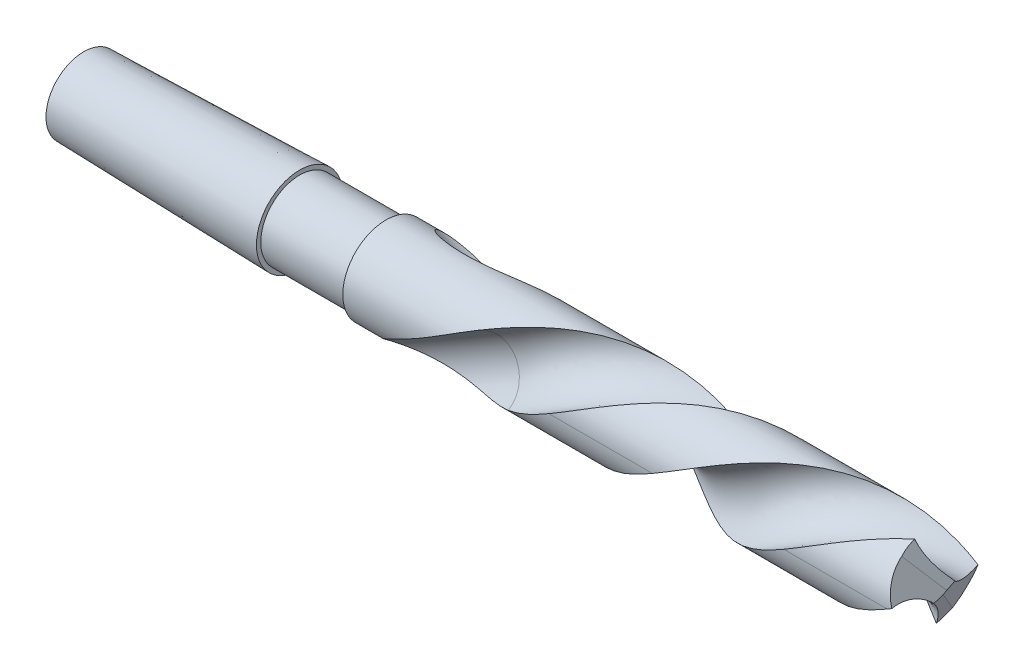
SolidWorks part; units mm, degrees
ref_plane "Ön Düzlem" through (0, 0, 0) normal (0, 0, 1) x (1, 0, 0)
ref_plane "Üst Düzlem" through (0, 0, 0) normal (0, 1, 0) x (1, 0, 0)
ref_plane "Sağ Düzlem" through (0, 0, 0) normal (1, 0, 0) x (0, 0, -1)
sketch "Çizim1" plane through (0, 0, 0) normal (0, 0, 1) x (1, 0, 0)
  line L9 (0, 0) -> (100, 0)
  line L10 (100, 0) -> (100, 5)
  line L11 (100, 5) -> (35, 5)
  line L12 (35, 5) -> (35, 4.5)
  line L13 (35, 4.5) -> (25, 4.5)
  line L14 (25, 4.5) -> (25, 5)
  line L15 (25, 5) -> (0, 4.37)
  line L16 (0, 4.37) -> (0, 0)
  point P2 (0, 0)
  dimension "D1" = 100
  dimension "D2" = 4.5
  dimension "D3" = 5
  dimension "D4" = 5
  dimension "D5" = 4.37
  dimension "D6" = 65
  dimension "D7" = 10
revolve "Döndür2" add sketch "Çizim1" angle 360 about L9
ref_plane "Düzlem2" through (51.25, 0, 0) normal (1, 0, 0) x (0, 0, -1)
ref_axis "Eksen3" through (100, 0, 0) along (-1, 0, 0)
ref_axis "Eksen4" through (51.25, 0, -5.5) along (0, 0, 1)
ref_plane "Düzlem3" through (38.4375, 22.1919, 0) normal (-0.866, -0.5, 0) x (0, 0, 1)
sketch "Çizim2" plane through (51.25, 0, 0) normal (1, 0, 0) x (0, 0, -1)
  circle A0 centre (0, 0) radius 5
  dimension "D1" = 10
curve "Helis/Spiral1" pitch 54.414 height 60 turns 1.1027
sketch "Çizim4" plane through (51.25, 0, 0) normal (1, 0, 0) x (0, 0, -1)
  circle A0 centre (0, 0) radius 5
  dimension "D1" = 10
curve "Helis/Spiral2" pitch 54.414 height 60 radius 5 left hand yes centre (51.25, 0, 0) axis (1, 0, 0) start towards (0, 0, 1)
sketch "Çizim5" plane through (38.4375, 22.1919, 0) normal (-0.866, -0.5, 0) x (0, 0, 1)
  line L0 (-5.5, -25.625) -> (5.5, -25.625) construction
  line L1 (0, -50) -> (0, -17.5) construction
  circle A0 centre (5, -25.625) radius 3.75
  dimension "D1" = 7.5
  dimension "D2" = 5
sweep "Kes-Süpür2" cut profiles "Çizim5" path "Helis/Spiral2" align with end faces yes
extrude "Kes-Ekstrüzyon3" cut sketch "Çizim5<2>" along normal through all
sketch "Çizim5<2>" plane through (38.4375, 22.1919, 0) normal (-0.866, -0.5, 0) x (0, 0, 1) same geometry as "Çizim5"
pattern_circular "Dairesel Kaplama2" count 2 over 360 about axis through (0, 0, 0) along (-1, 0, 0) of "Kes-Ekstrüzyon3", "Kes-Süpür2"
sketch "Çizim6" plane through (100, 0, 0) normal (1, 0, 0) x (0, 0, -1)
  line L0 (3.9159, 3.1089) -> (-3.9159, -3.1089)
  circle A0 centre (0, 0) radius 5 construction
  circle A1 centre (0, 0) radius 1.25
  dimension "D1" = 10
  dimension "D2" = 2.5
ref_axis "Eksen5" through (100, 3.1089, -3.9159) along (0, -0.6218, 0.7832)
ref_plane "Düzlem4" through (0, 0, 0) normal (0, 0.7832, 0.6218) x (1, 0, 0)
ref_plane "Düzlem5" through (0, 0, 0) normal (0, 0.6218, -0.7832) x (-1, 0, 0)
sketch "Çizim7" plane through (0, 0, 0) normal (0, 0.6218, -0.7832) x (-1, 0, 0)
  line L0 (-95.8579, -10) -> (-110, -10)
  line L1 (-110, -10) -> (-110, 10)
  line L2 (-110, 0) -> (-100, 0)
  line L3 (-100, 1.25) -> (-100, -1.25) construction
  line L4 (-100, 0) -> (-95.8579, -10)
  line L5 (5.5, 0) -> (-5.5, 0) construction
  line L6 (-95.8579, 10) -> (-110, 10)
  line L7 (-100, 0) -> (-95.8579, 10)
  dimension "D1" = 10
  dimension "D2" = 10
  dimension "D3" = 67.5
extrude "Kes-Ekstrüzyon4" cut sketch "Çizim7" against normal mid plane 20 contours L2 L7 L6 L1 | L4 L2 L1 L0 region at (103.9052, -4.1399, -3.2867) region at (103.9052, 4.1399, 3.2867)
ref_plane "Düzlem6" through (14.6447, -27.6898, -21.9835) normal (-0.3827, 0.7236, 0.5745) x (0, -0.6218, 0.7832)
sketch "Çizim8" plane through (14.6447, -27.6898, -21.9835) normal (-0.3827, 0.7236, 0.5745) x (0, -0.6218, 0.7832)
  line L0 (-5, 92.406) -> (5, 92.406)
  line L1 (5, 92.406) -> (-0.224, 92.1322)
  line L2 (-0.224, 92.1322) -> (-5, 91.2901)
  line L3 (-5, 91.2901) -> (-5, 92.406)
  line L4 (0, 92.388) -> (0, 32.3358) construction
  dimension "D1" = 10
  dimension "D2" = 5
  dimension "D3" = 3
  dimension "D4" = 10
extrude "Kes-Ekstrüzyon5" cut sketch "Çizim8" against normal mid plane 20
pattern_circular "Dairesel Kaplama3" count 2 over 360 about axis through (100, 0, 0) along (-1, 0, 0) of "Kes-Ekstrüzyon5"
